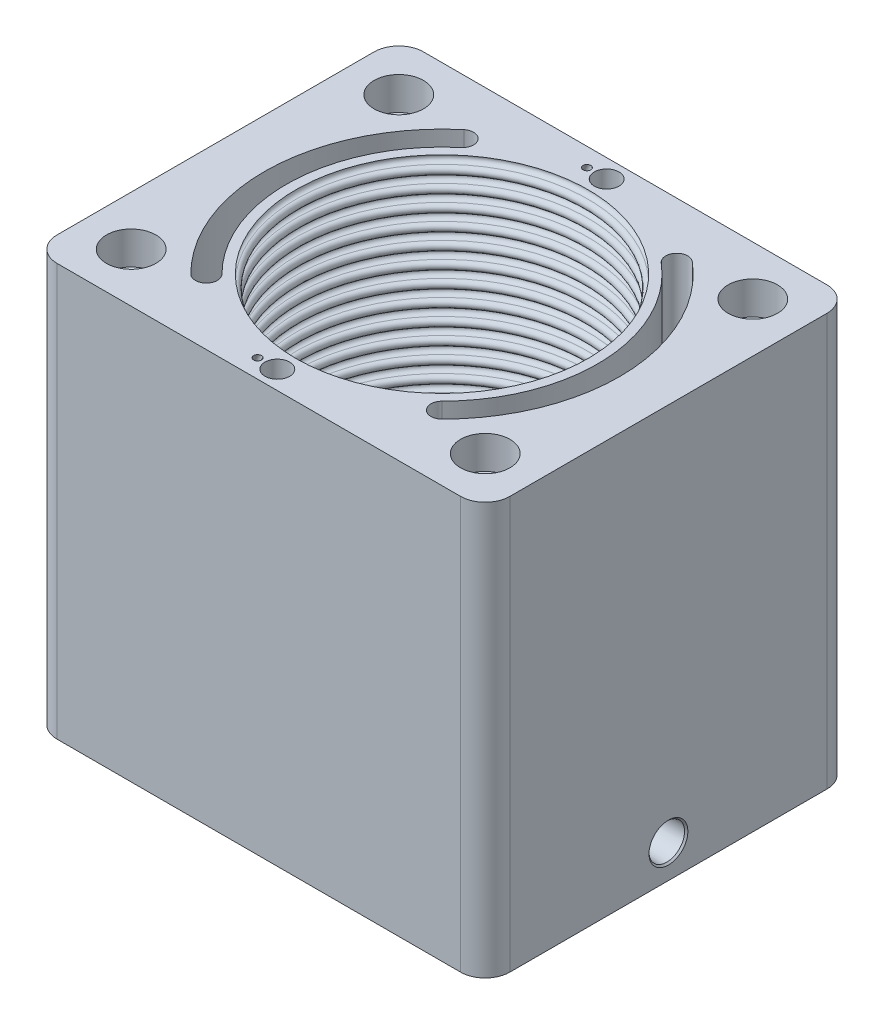
SolidWorks part; units mm, degrees
ref_plane "Front Plane" through (0, 0, 0) normal (0, 0, 1) x (1, 0, 0)
ref_plane "Top Plane" through (0, 0, 0) normal (0, 1, 0) x (1, 0, 0)
ref_plane "Right Plane" through (0, 0, 0) normal (1, 0, 0) x (0, 0, -1)
sketch "Sketch3" plane through (0, 0, 0) normal (0, 1, 0) x (1, 0, 0)
  line L1 (-87.3125, 70.6437) -> (87.3125, 70.6437)
  line L2 (-87.3125, 70.6437) -> (-87.3125, -70.6438)
  line L3 (-87.3125, -70.6438) -> (87.3125, -70.6438)
  line L4 (87.3125, 70.6437) -> (87.3125, -70.6438)
  line L5 (-87.3125, 70.6437) -> (87.3125, -70.6438) construction
  line L6 (-87.3125, -70.6438) -> (87.3125, 70.6437) construction
  circle A0 centre (0, 0) radius 57.9437
  point P0 (0, 0)
  dimension "D3" = 115.8875
  dimension "D1" = 174.625
  dimension "D2" = 141.2875
extrude "Boss-Extrude1" add sketch "Sketch3" along normal blind 158.8897
fillet "Fillet1" radius 9.525 4 edges at (87.3125, 79.4449, 70.6438) (87.3125, 79.4449, -70.6437) (-87.3125, 79.4449, -70.6437) (-87.3125, 79.4449, 70.6438)
sketch "Sketch4" plane through (0, 0, 0) normal (0, -1, 0) x (1, 0, 0)
  line L1 (-68.2625, -51.5937) -> (68.2625, -51.5937) construction
  line L2 (-68.2625, -51.5937) -> (-68.2625, 51.5937) construction
  line L3 (-68.2625, 51.5937) -> (68.2625, 51.5937) construction
  line L4 (68.2625, -51.5937) -> (68.2625, 51.5937) construction
  line L5 (-68.2625, -51.5937) -> (68.2625, 51.5937) construction
  line L6 (-68.2625, 51.5937) -> (68.2625, -51.5937) construction
  line L7 (77.7875, -70.6437) -> (-77.7875, -70.6437) construction
  line L8 (-87.3125, -61.1187) -> (-87.3125, 61.1188) construction
  circle A0 centre (-68.2625, -51.5937) radius 6.35
  circle A1 centre (-68.2625, 51.5937) radius 6.35
  circle A2 centre (68.2625, 51.5937) radius 6.35
  circle A3 centre (68.2625, -51.5937) radius 6.35
  point P0 (0, 0)
  dimension "D3" = 12.7
  dimension "D1" = 19.05
  dimension "D2" = 19.05
extrude "Cut-Extrude1" cut sketch "Sketch4" against normal through all
sketch "Sketch5" plane through (0, 158.8897, 0) normal (0, 1, 0) x (1, 0, 0)
  circle A0 centre (68.2625, 51.5937) radius 9.525
  circle A1 centre (68.2625, -51.5937) radius 9.525
  circle A2 centre (-68.2625, -51.5937) radius 9.525
  circle A3 centre (-68.2625, 51.5937) radius 9.525
  dimension "D1" = 19.05
extrude "Cut-Extrude2" cut sketch "Sketch5" against normal blind 12.7
sketch "Sketch6" plane through (0, 0, 0) normal (1, 0, 0) x (0, 0, -1)
  line L0 (57.9437, 158.8897) -> (-57.9438, 158.8897) construction
  line L1 (57.9437, 158.8897) -> (-57.9438, 158.8897) construction
  line L2 (0, 158.8897) -> (0, 0) construction
  line L3 (57.9437, 158.8897) -> (57.9437, 0) construction
  line L4 (61.1187, 0) -> (-61.1188, 0) construction
  line L5 (56.3562, 152.5397) -> (57.9437, 152.5397)
  line L6 (57.9437, 152.5397) -> (57.9437, 158.8897)
  line L7 (57.9437, 158.8897) -> (56.3562, 158.8897)
  arc A0 (56.3562, 158.8897) -> (56.3562, 155.7147) centre (56.3562, 157.3022) cw
  arc A1 (56.3562, 155.7147) -> (56.3562, 152.5397) centre (56.3562, 154.1272) ccw
  dimension "D1" = 1.5875
  dimension "D2" = 1.5875
revolve "Revolve1" add sketch "Sketch6" angle 360 about L2 region at (0, 154.2373, -56.5659) region at (0, 158.5351, -57.5892)
pattern_linear "LPattern1" count 24 spacing 6.35 along (0, -1, 0) of "Revolve1"
sketch "Sketch7" plane through (0, 0, 0) normal (1, 0, 0) x (0, 0, -1)
  line L0 (-56.3563, 6.4897) -> (56.3562, 6.4897) construction
  line L1 (-57.9438, 0) -> (57.9437, 0) construction
  line L2 (-56.3563, 6.4897) -> (56.3562, 6.4897) construction
  line L3 (-57.9438, 0) -> (57.9437, 0) construction
  line L4 (56.3562, 6.4897) -> (57.9437, 6.4897)
  line L5 (57.9437, 4.9022) -> (57.9437, 6.4897)
  line L6 (54.7687, 1.7272) -> (54.7687, 0)
  line L7 (57.9437, 4.9022) -> (57.9437, 0)
  line L8 (57.9437, 0) -> (54.7687, 0)
  line L9 (0, 0) -> (0, 188.0001) construction
  arc A0 (56.3562, 6.4897) -> (56.3562, 3.3147) centre (56.3562, 4.9022) cw
  arc A1 (56.3562, 3.3147) -> (54.7687, 1.7272) centre (56.3562, 1.7272) ccw
  dimension "D1" = 1.5875
revolve "Revolve2" add sketch "Sketch7" angle 360 about L9 region at (0, 1.6938, -56.483) region at (0, 6.1351, -57.5892)
sketch "Sketch9" plane through (0, 158.8897, 0) normal (0, 1, 0) x (1, 0, 0)
  line L0 (0, 0) -> (-100.7844, 0) construction
  line L1 (0, 0) -> (94.1471, -94.1471) construction
  line L2 (0, 0) -> (71.4803, 85.1869) construction
  line L3 (0, 0) -> (0, -74.221) construction
  arc A0 (42.4264, -42.4264) -> (38.5673, 45.9627) centre (0, 0) ccw
  arc A1 (48.4368, -48.4368) -> (44.031, 52.4741) centre (0, 0) ccw
  arc A2 (42.4264, -42.4264) -> (48.4368, -48.4368) centre (45.4316, -45.4316) ccw
  arc A3 (44.031, 52.4741) -> (38.5673, 45.9627) centre (41.2991, 49.2184) ccw
  arc A16 (-44.031, 52.4741) -> (-38.5673, 45.9627) centre (-41.2991, 49.2184) cw
  arc A17 (-42.4264, -42.4264) -> (-48.4368, -48.4368) centre (-45.4316, -45.4316) cw
  arc A18 (-48.4368, -48.4368) -> (-44.031, 52.4741) centre (0, 0) cw
  arc A19 (-42.4264, -42.4264) -> (-38.5673, 45.9627) centre (0, 0) cw
  point P33 (0, 0)
  dimension "D1" = 120.0001
  dimension "D2" = 8.5
  dimension "D3" = 45
  dimension "D4" = 95
extrude "Cut-Extrude3" cut sketch "Sketch9" against normal through all contours A3 A0 A2 A1 | A16 A19 A17 A18
sketch "Sketch11" plane through (0, 0, 0) normal (1, 0, 0) x (0, 0, -1)
  line L0 (64, 16.7) -> (64, 0) construction
  line L1 (61.1187, 0) -> (70.6437, 0) construction
  line L2 (60, 12.7) -> (60, 0)
  line L3 (-61.1188, 0) -> (61.1187, 0) construction
  line L4 (68, 12.7) -> (68, 0)
  line L5 (68, 0) -> (60, 0)
  arc A0 (68, 12.7) -> (60, 12.7) centre (64, 12.7) ccw
  dimension "D1" = 16.7
  dimension "D2" = 12.7
  dimension "D3" = 60
sketch "Sketch12" plane through (0, 0, 0) normal (0, -1, 0) x (1, 0, 0)
  line L0 (38.5673, -45.9627) -> (44.031, -52.4741) construction
  line L1 (-38.5673, -45.9627) -> (-44.031, -52.4741) construction
  arc A2 (-41.2991, -49.2184) -> (41.2991, -49.2184) centre (0, 0) ccw
  point P6 (41.2991, -49.2184)
sweep "Cut-Sweep1" cut profiles "Sketch11" path "Sketch12"
hole_wizard "1/4 NPT Tapped Hole1" positions "Sketch13" profile "Sketch14" size "1/4" standard "ANSI Inch" end condition up to next
sketch "Sketch13" plane through (87.3125, 0, 0) normal (1, 0, 0) x (0, 0, -1)
  line L0 (-61.1188, 0) -> (61.1187, 0) construction
  point P0 (0, 12.7)
  dimension "D1" = 12.7
sketch "Sketch14" plane through (87.3125, 12.7, 0) normal (0, 1, 0) x (0, 0, -1)
  line L0 (0, 0) -> (0, 18.8125)
  line L1 (0, 18.8125) -> (5.5626, 18.8125)
  line L3 (5.5626, 18.8125) -> (5.5626, 10.0203)
  line L4 (5.5626, 10.0203) -> (6.577, 10.0203)
  line L5 (6.577, 10.0203) -> (6.858, 0.635)
  line L6 (6.858, 0.635) -> (7.493, 0)
  line L7 (7.493, 0) -> (0, 0)
  line L8 (0, -6.35) -> (0, 107.95) construction
  line L9 (-6.858, 0.635) -> (-7.493, 0) construction
  line L11 (-5.5626, 10.0203) -> (-6.577, 10.0203) construction
  line L12 (-6.577, 10.0203) -> (-6.858, 0.635) construction
  dimension "Thru Tap Drill Dia." = 11.1252
  dimension "Thru Tap Drill Depth" = 18.8125
  dimension "Thread Dia." = 13.716
  dimension "Thread Angle" = 3.43
  dimension "Thread Depth" = 10.0203
  dimension "Near C'Sink Dia." = 14.986
  dimension "Near C'Sink Angle" = 90
sketch "Sketch15" plane through (0, 158.8897, 0) normal (0, 1, 0) x (1, 0, 0)
  line L1 (-77.7875, -70.6438) -> (77.7875, -70.6438) construction
  line L2 (0, 63.5) -> (0, -63.5) construction
  line L3 (87.3125, 0) -> (-87.3125, 0) construction
  line L4 (87.3125, -61.1188) -> (87.3125, 61.1187) construction
  line L5 (-87.3125, 61.1187) -> (-87.3125, -61.1188) construction
  circle A0 centre (0, 63.5) radius 4.7625
  circle A1 centre (0, -63.5) radius 4.7625
  point P14 (0, 0)
  point P15 (0, 0)
  dimension "D1" = 9.525
  dimension "D3" = 7.1437
extrude "Cut-Extrude4" cut sketch "Sketch15" against normal blind 9.525
sketch "Sketch16" plane through (0, 158.8897, 0) normal (0, 1, 0) x (1, 0, 0)
  line L0 (-7.62, 63.5) -> (0, 63.5) construction
  circle A0 centre (-7.62, 63.5) radius 1.4986
  dimension "D2" = 2.9972
  dimension "D1" = 7.62
sketch "Sketch17" plane through (0, 0, 0) normal (0, -1, 0) x (1, 0, 0)
  line L0 (-87.3125, -61.1187) -> (-87.3125, 61.1188) construction
  line L1 (-74.6125, -63.5) -> (-74.6125, -70.6437) construction
  line L2 (77.7875, -70.6437) -> (-77.7875, -70.6437) construction
  line L3 (-7.62, -63.5) -> (-74.6125, -63.5) construction
  circle A0 centre (-74.6125, -63.5) radius 1.4986
  circle A1 centre (-7.62, -63.5) radius 1.4986 construction
  dimension "D1" = 7.1438
  dimension "D2" = 12.7
ref_plane "Plane1" through (0, 0, -63.5) normal (0, 0, 1) x (1, 0, 0)
loft "Cut-Loft1" cut profiles "Sketch16", "Sketch17" connector at (-9.1122, 158.8897, -63.3617) connector at (-76.1108, 0, -63.4698)
mirror "Mirror2" about plane through (0, 0, 0) normal (0, 0, 1) of "Cut-Loft1"
sketch "Sketch18" plane through (0, 0, 0) normal (0, -1, 0) x (-1, 0, 0)
  circle A0 centre (-68.2625, -51.5937) radius 8.3344
  circle A1 centre (-68.2625, 51.5937) radius 8.3344
  circle A2 centre (68.2625, -51.5938) radius 8.3344
  circle A3 centre (68.2625, 51.5937) radius 8.3344
  dimension "D1" = 16.6687
extrude "Cut-Extrude5" cut sketch "Sketch18" against normal blind 6.35
